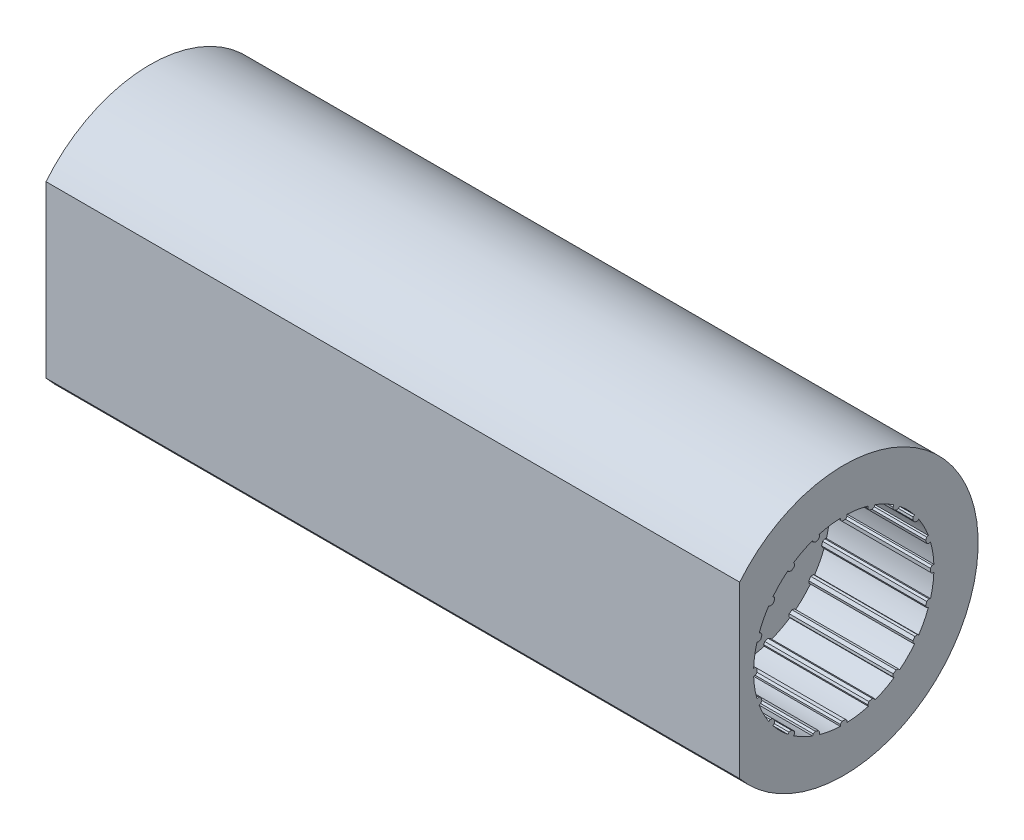
SolidWorks part; units mm, degrees
ref_plane "Alzado" through (0, 0, 0) normal (1, 0, 0) x (0, 1, 0)
ref_plane "Planta" through (0, 0, 0) normal (0, 0, 1) x (0, 1, 0)
ref_plane "Vista lateral" through (0, 0, 0) normal (0, 1, 0) x (-1, 0, 0)
sketch "Croquis1" plane through (0, 0, 0) normal (1, 0, 0) x (0, 1, 0)
  line L0 (2.4527, 3) -> (-2.4527, 3)
  arc A0 (-2.4527, 3) -> (2.4527, 3) centre (0, 0) ccw
  circle A1 centre (0, 0) radius 2.25
  circle A2 centre (0, 0) radius 1.25
  dimension "D1" = 7.75
  dimension "D3" = 4.5
  dimension "D4" = 2.5
  dimension "D2" = 3
extrude "Saliente-Extruir1" add sketch "Croquis1" along normal blind 20 contours A2 | A1 A2 | L0 A0 A1 region at (0, 0, -3.7714) region at (0, -2.1864, 0) region at (0, 0, 0)
sketch "Croquis2" plane through (20, 0, 0) normal (1, 0, 0) x (0, 1, 0)
  line L0 (-2.6, 0) -> (-2.4981, 0) construction
  line L1 (-2.4981, 0) -> (-2.4981, -0.05)
  line L2 (-2.5481, -0.1) -> (-2.5981, -0.1)
  line L3 (-2.4981, 0) -> (-2.4981, 0.05)
  line L4 (-2.5481, 0.1) -> (-2.5981, 0.1)
  line L5 (-2.4981, 0.05) -> (-2.5481, 0.1)
  line L6 (-2.4981, -0.05) -> (-2.5481, -0.1)
  line L7 (-2.4543, -0.6923) -> (-2.5018, -0.7077)
  line L8 (-2.3913, -0.7244) -> (-2.4543, -0.6923)
  line L9 (-2.3758, -0.7719) -> (-2.3913, -0.7244)
  line L10 (-2.3758, -0.7719) -> (-2.3604, -0.8195)
  line L11 (-2.3604, -0.8195) -> (-2.3925, -0.8825)
  line L12 (-2.3925, -0.8825) -> (-2.44, -0.898)
  line L13 (-2.1202, -1.4168) -> (-2.1607, -1.4462)
  line L14 (-2.0504, -1.4279) -> (-2.1202, -1.4168)
  line L15 (-2.021, -1.4683) -> (-2.0504, -1.4279)
  line L16 (-2.021, -1.4683) -> (-1.9916, -1.5088)
  line L17 (-1.9916, -1.5088) -> (-2.0027, -1.5786)
  line L18 (-2.0027, -1.5786) -> (-2.0431, -1.608)
  line L19 (-1.5786, -2.0027) -> (-1.608, -2.0431)
  line L20 (-1.5088, -1.9916) -> (-1.5786, -2.0027)
  line L21 (-1.4683, -2.021) -> (-1.5088, -1.9916)
  line L22 (-1.4683, -2.021) -> (-1.4279, -2.0504)
  line L23 (-1.4279, -2.0504) -> (-1.4168, -2.1202)
  line L24 (-1.4168, -2.1202) -> (-1.4462, -2.1607)
  line L25 (-0.8825, -2.3925) -> (-0.898, -2.44)
  line L26 (-0.8195, -2.3604) -> (-0.8825, -2.3925)
  line L27 (-0.7719, -2.3758) -> (-0.8195, -2.3604)
  line L28 (-0.7719, -2.3758) -> (-0.7244, -2.3913)
  line L29 (-0.7244, -2.3913) -> (-0.6923, -2.4543)
  line L30 (-0.6923, -2.4543) -> (-0.7077, -2.5018)
  line L31 (-0.1, -2.5481) -> (-0.1, -2.5981)
  line L32 (-0.05, -2.4981) -> (-0.1, -2.5481)
  line L33 (0, -2.4981) -> (-0.05, -2.4981)
  line L34 (0, -2.4981) -> (0.05, -2.4981)
  line L35 (0.05, -2.4981) -> (0.1, -2.5481)
  line L36 (0.1, -2.5481) -> (0.1, -2.5981)
  line L37 (0.6923, -2.4543) -> (0.7077, -2.5018)
  line L38 (0.7244, -2.3913) -> (0.6923, -2.4543)
  line L39 (0.7719, -2.3758) -> (0.7244, -2.3913)
  line L40 (0.7719, -2.3758) -> (0.8195, -2.3604)
  line L41 (0.8195, -2.3604) -> (0.8825, -2.3925)
  line L42 (0.8825, -2.3925) -> (0.898, -2.44)
  line L43 (1.4168, -2.1202) -> (1.4462, -2.1607)
  line L44 (1.4279, -2.0504) -> (1.4168, -2.1202)
  line L45 (1.4683, -2.021) -> (1.4279, -2.0504)
  line L46 (1.4683, -2.021) -> (1.5088, -1.9916)
  line L47 (1.5088, -1.9916) -> (1.5786, -2.0027)
  line L48 (1.5786, -2.0027) -> (1.608, -2.0431)
  line L49 (2.0027, -1.5786) -> (2.0431, -1.608)
  line L50 (1.9916, -1.5088) -> (2.0027, -1.5786)
  line L51 (2.021, -1.4683) -> (1.9916, -1.5088)
  line L52 (2.021, -1.4683) -> (2.0504, -1.4279)
  line L53 (2.0504, -1.4279) -> (2.1202, -1.4168)
  line L54 (2.1202, -1.4168) -> (2.1607, -1.4462)
  line L55 (2.3925, -0.8825) -> (2.44, -0.898)
  line L56 (2.3604, -0.8195) -> (2.3925, -0.8825)
  line L57 (2.3758, -0.7719) -> (2.3604, -0.8195)
  line L58 (2.3758, -0.7719) -> (2.3913, -0.7244)
  line L59 (2.3913, -0.7244) -> (2.4543, -0.6923)
  line L60 (2.4543, -0.6923) -> (2.5018, -0.7077)
  line L61 (2.5481, -0.1) -> (2.5981, -0.1)
  line L62 (2.4981, -0.05) -> (2.5481, -0.1)
  line L63 (2.4981, 0) -> (2.4981, -0.05)
  line L64 (2.4981, 0) -> (2.4981, 0.05)
  line L65 (2.4981, 0.05) -> (2.5481, 0.1)
  line L66 (2.5481, 0.1) -> (2.5981, 0.1)
  line L67 (2.4543, 0.6923) -> (2.5018, 0.7077)
  line L68 (2.3913, 0.7244) -> (2.4543, 0.6923)
  line L69 (2.3758, 0.7719) -> (2.3913, 0.7244)
  line L70 (2.3758, 0.7719) -> (2.3604, 0.8195)
  line L71 (2.3604, 0.8195) -> (2.3925, 0.8825)
  line L72 (2.3925, 0.8825) -> (2.44, 0.898)
  line L73 (2.1202, 1.4168) -> (2.1607, 1.4462)
  line L74 (2.0504, 1.4279) -> (2.1202, 1.4168)
  line L75 (2.021, 1.4683) -> (2.0504, 1.4279)
  line L76 (2.021, 1.4683) -> (1.9916, 1.5088)
  line L77 (1.9916, 1.5088) -> (2.0027, 1.5786)
  line L78 (2.0027, 1.5786) -> (2.0431, 1.608)
  line L79 (1.5786, 2.0027) -> (1.608, 2.0431)
  line L80 (1.5088, 1.9916) -> (1.5786, 2.0027)
  line L81 (1.4683, 2.021) -> (1.5088, 1.9916)
  line L82 (1.4683, 2.021) -> (1.4279, 2.0504)
  line L83 (1.4279, 2.0504) -> (1.4168, 2.1202)
  line L84 (1.4168, 2.1202) -> (1.4462, 2.1607)
  line L85 (0.8825, 2.3925) -> (0.898, 2.44)
  line L86 (0.8195, 2.3604) -> (0.8825, 2.3925)
  line L87 (0.7719, 2.3758) -> (0.8195, 2.3604)
  line L88 (0.7719, 2.3758) -> (0.7244, 2.3913)
  line L89 (0.7244, 2.3913) -> (0.6923, 2.4543)
  line L90 (0.6923, 2.4543) -> (0.7077, 2.5018)
  line L91 (0.1, 2.5481) -> (0.1, 2.5981)
  line L92 (0.05, 2.4981) -> (0.1, 2.5481)
  line L93 (0, 2.4981) -> (0.05, 2.4981)
  line L94 (0, 2.4981) -> (-0.05, 2.4981)
  line L95 (-0.05, 2.4981) -> (-0.1, 2.5481)
  line L96 (-0.1, 2.5481) -> (-0.1, 2.5981)
  line L97 (-0.6923, 2.4543) -> (-0.7077, 2.5018)
  line L98 (-0.7244, 2.3913) -> (-0.6923, 2.4543)
  line L99 (-0.7719, 2.3758) -> (-0.7244, 2.3913)
  line L100 (-0.7719, 2.3758) -> (-0.8195, 2.3604)
  line L101 (-0.8195, 2.3604) -> (-0.8825, 2.3925)
  line L102 (-0.8825, 2.3925) -> (-0.898, 2.44)
  line L103 (-1.4168, 2.1202) -> (-1.4462, 2.1607)
  line L104 (-1.4279, 2.0504) -> (-1.4168, 2.1202)
  line L105 (-1.4683, 2.021) -> (-1.4279, 2.0504)
  line L106 (-1.4683, 2.021) -> (-1.5088, 1.9916)
  line L107 (-1.5088, 1.9916) -> (-1.5786, 2.0027)
  line L108 (-1.5786, 2.0027) -> (-1.608, 2.0431)
  line L109 (-2.0027, 1.5786) -> (-2.0431, 1.608)
  line L110 (-1.9916, 1.5088) -> (-2.0027, 1.5786)
  line L111 (-2.021, 1.4683) -> (-1.9916, 1.5088)
  line L112 (-2.021, 1.4683) -> (-2.0504, 1.4279)
  line L113 (-2.0504, 1.4279) -> (-2.1202, 1.4168)
  line L114 (-2.1202, 1.4168) -> (-2.1607, 1.4462)
  line L115 (-2.3925, 0.8825) -> (-2.44, 0.898)
  line L116 (-2.3604, 0.8195) -> (-2.3925, 0.8825)
  line L117 (-2.3758, 0.7719) -> (-2.3604, 0.8195)
  line L118 (-2.3758, 0.7719) -> (-2.3913, 0.7244)
  line L119 (-2.3913, 0.7244) -> (-2.4543, 0.6923)
  line L120 (-2.4543, 0.6923) -> (-2.5018, 0.7077)
  circle A0 centre (0, 0) radius 2.6
  point P6 (-2.4981, -0.1)
  point P8 (-2.4981, 0.1)
  dimension "D1" = 5.2
  dimension "D2" = 0.2
  dimension "D3" = 0.1
  dimension "D4" = 20
extrude "Cortar-Extruir2" cut sketch "Croquis2" against normal blind 3 contours L36 A0 L37 L38 L39 L40 L41 L42 L43 L44 L45 L46 L47 L48 L49 L50 L51 L52 L53 L54 L55 L56 L57 L58 L59 L60 L61 L62 L63 L64 L65 L66 L67 L68 L69 L70 L71 L72 L73 L74 L75 L76 L77 L78 region at (20, 0, 0)
extrude "Cortar-Extruir1" cut sketch "Croquis1<3>" along normal offset from surface (15.5 mm away) 1.5 contours A1 A2 region at (0, -2.1864, 0) up to face at (17, 0, 0)
sketch "Croquis1<3>" plane through (0, 0, 0) normal (1, 0, 0) x (0, 1, 0) same geometry as "Croquis1"
extrude "Cortar-Extruir4" cut sketch "Croquis1<5>" along normal up to surface (17 mm away) contours A2 region at (0, 0, 0) up to face at (17, 0, 0)
sketch "Croquis1<5>" plane through (0, 0, 0) normal (1, 0, 0) x (0, 1, 0) same geometry as "Croquis1"
